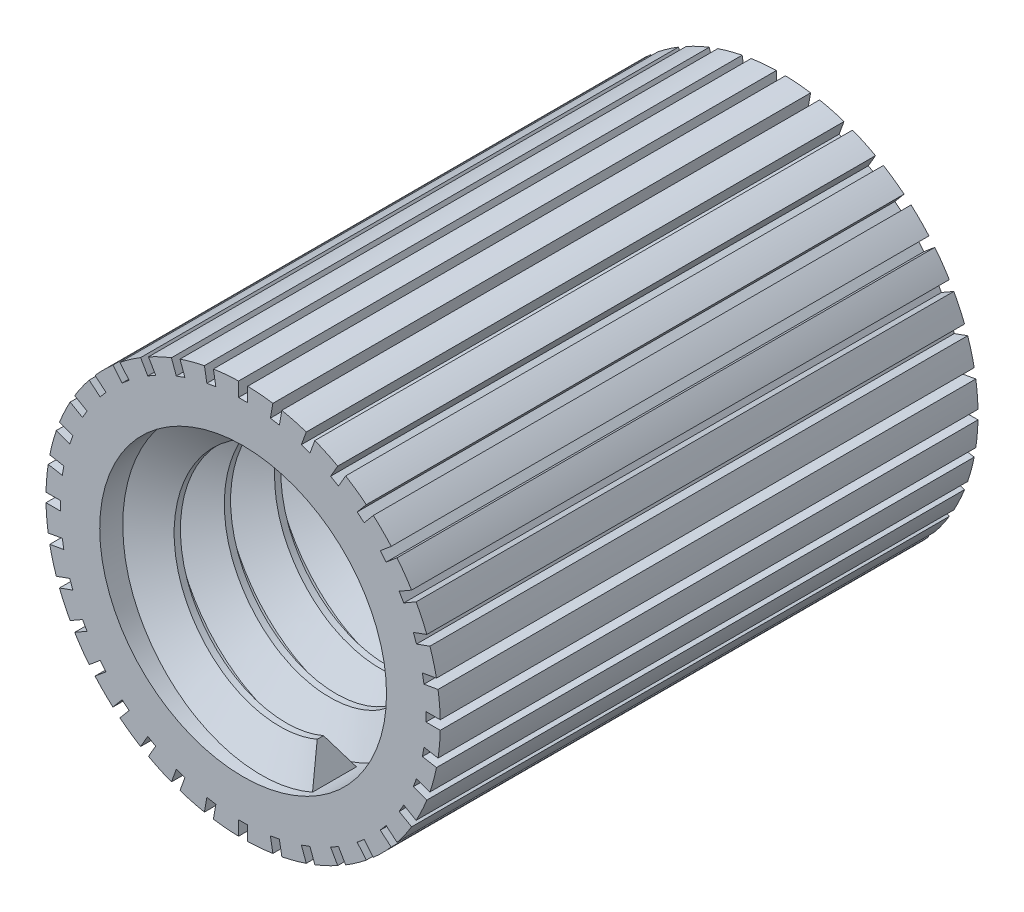
SolidWorks part; units mm, degrees
material "Brass"
ref_plane "Front Plane" through (0, 0, 0) normal (0, 0, 1) x (1, 0, 0)
ref_plane "Top Plane" through (0, 0, 0) normal (0, 1, 0) x (1, 0, 0)
ref_plane "Right Plane" through (0, 0, 0) normal (1, 0, 0) x (0, 0, -1)
sketch "Sketch2" plane through (0, 0, 0) normal (0, 0, -1) x (-1, 0, 0)
  circle A0 centre (0, 0) radius 2.75
  point P3 (0, 0)
  point P4 (0, 0)
  dimension "C" = 5.5
extrude "Extrude2" add sketch "Sketch2" along normal blind 7.5
sketch "Sketch3" plane through (0, 0, -7.5) normal (0, 0, -1) x (-1, 0, 0)
  line L0 (0, 2.55) -> (0, 2.75)
  circle A0 centre (0, 0) radius 2.75 construction
  circle A2 centre (0, 0) radius 2.55
  circle A3 centre (0, 0) radius 2.55 construction
  point P3 (0, 2.7)
  point P8 (0, 0)
  dimension "D1" = 0.2
extrude "Cut-Extrude-Thin1" cut sketch "Sketch3" against normal up to surface (7.5 mm away) thin up to face at (-2.75, 0, 0) thin type mid plane wall 0.127
pattern_circular "CirPattern1" count 36 over 360 about axis through (0, 0, -7.5) along (0, 0, 1) of "Cut-Extrude-Thin1"
sketch "Sketch5" plane through (0, 0, -7.5) normal (0, 0, -1) x (-1, 0, 0)
  circle A2 centre (0, 0) radius 2.35
  circle A3 centre (0, 0) radius 2.35
  dimension "D1" = 0.2
sketch "Sketch7" plane through (0, 0, 0) normal (0, 0, 1) x (1, 0, 0)
  circle A0 centre (0, 0) radius 2
  dimension "Thread Od" = 4
extrude "Cut-Extrude3" cut sketch "Sketch7" against normal through all
sketch "Sketch8" plane through (0, 0, -7.5) normal (0, 0, -1) x (-1, 0, 0)
  circle A0 centre (0, 0) radius 2 construction
  circle A1 centre (0, 0) radius 2
curve "Helix/Spiral1" pitch 0.7 height 7.4 radius 2 centre (0, 0, -7.5) axis (0, 0, 1) start towards (0, 1, 0) parameters "pitch"=0.7
sketch "Sketch9" plane through (0, 0, 0) normal (1, 0, 0) x (0, 0, -1)
  line L0 (8.1125, 2) -> (7.85, 1.5453)
  line L1 (7.85, 1.5453) -> (7.7625, 1.5453)
  line L2 (7.7625, 1.5453) -> (7.5, 2)
  line L3 (8.1125, 2) -> (7.5, 2)
  line L4 (7.8063, 2) -> (7.8063, 1.5453) construction
  line L5 (7.9812, 1.7727) -> (7.6313, 1.7727) construction
  line L6 (7.5, -2) -> (7.5, 2) construction
  dimension "D1" = 60
  dimension "D2" = 0.0875
  dimension "D3" = 0.35
sweep "Sweep1" add profiles "Sketch9" path "Helix/Spiral1"
sketch "Sketch11" plane through (0, 0, -7.5) normal (0, 0, -1) x (-1, 0, 0)
  arc A0 (0.0635, -2.7493) -> (0.4149, -2.7185) centre (0, 0) ccw construction
  circle A1 centre (0, 0) radius 2.75
extrude "Cut-Extrude5" cut sketch "Sketch11" along normal through all
sketch "Sketch14" plane through (0, 0, -7.5) normal (0, 0, -1) x (-1, 0, 0)
  circle A2 centre (0, 0) radius 2.0508
  circle A3 centre (0, 0) radius 2.0508
  dimension "D1" = 0.0508
extrude "Cut-Extrude7" cut sketch "Sketch14" against normal through all draft 45
equation "\"D2@Sketch9\" = \"pitch@Helix/Spiral1\"*.125"
equation "\"D3@Sketch9\" = \"pitch@Helix/Spiral1\"*.50"
